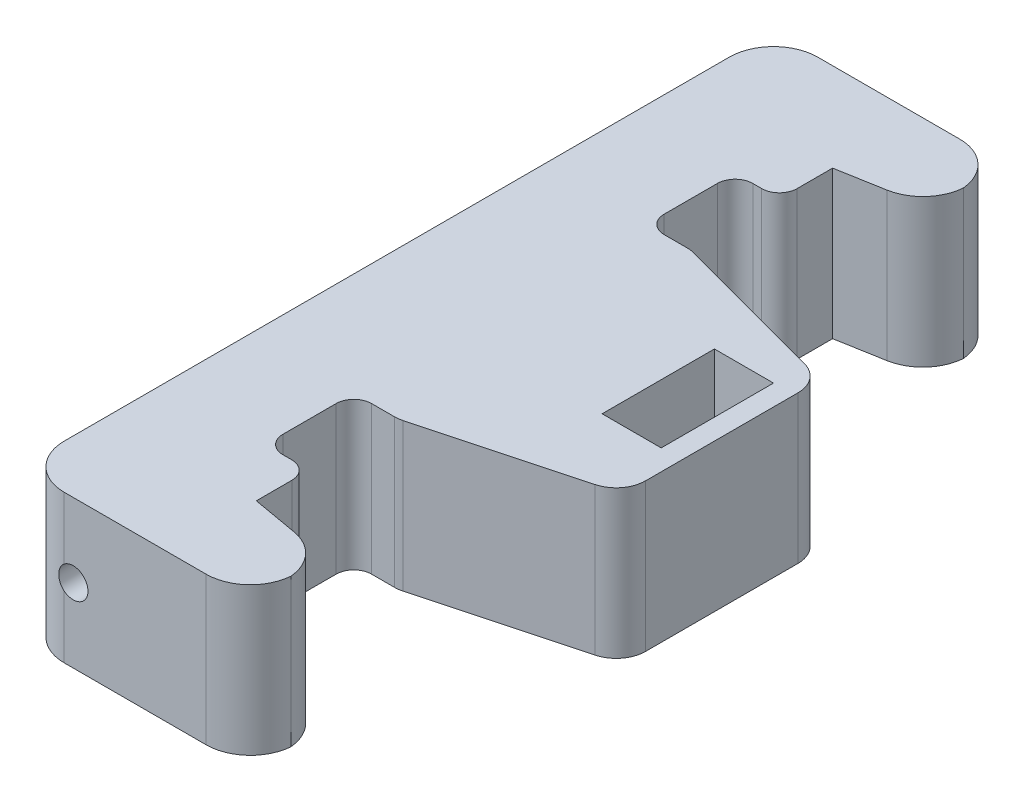
SolidWorks part; units mm, degrees
ref_plane "Front Plane" through (0, 0, 0) normal (0, 0, 1) x (1, 0, 0)
ref_plane "Top Plane" through (0, 0, 0) normal (0, 1, 0) x (1, 0, 0)
ref_plane "Right Plane" through (0, 0, 0) normal (1, 0, 0) x (0, 0, -1)
sketch "Sketch1" plane through (0, 0, 0) normal (0, 1, 0) x (1, 0, 0)
  line L0 (-13.97, 32.385) -> (13.97, -32.385) construction
  line L1 (-13.97, 32.385) -> (13.97, 32.385)
  line L2 (-13.97, 32.385) -> (-13.97, -32.385)
  line L3 (-13.97, -32.385) -> (13.97, -32.385)
  line L4 (13.97, 32.385) -> (13.97, -32.385)
  line L5 (-13.97, -32.385) -> (13.97, 32.385) construction
  line L7 (13.97, 32.385) -> (5.842, 32.385)
  line L8 (13.97, 32.385) -> (13.97, 12.573)
  line L9 (13.97, 12.573) -> (5.842, 12.573)
  line L10 (5.842, 32.385) -> (5.842, 12.573)
  line L11 (13.97, -32.385) -> (5.842, -32.385)
  line L12 (13.97, -32.385) -> (13.97, -12.573)
  line L13 (13.97, -12.573) -> (5.842, -12.573)
  line L14 (5.842, -32.385) -> (5.842, -12.573)
  line L15 (5.842, 12.573) -> (-1.27, 12.573)
  line L16 (5.842, 12.573) -> (5.842, 24.765)
  line L17 (5.842, 24.765) -> (-1.27, 24.765)
  line L18 (-1.27, 12.573) -> (-1.27, 24.765)
  line L23 (5.842, -12.573) -> (-1.27, -12.573)
  line L24 (5.842, -12.573) -> (5.842, -24.765)
  line L25 (5.842, -24.765) -> (-1.27, -24.765)
  line L26 (-1.27, -12.573) -> (-1.27, -24.765)
  line L28 (-1.27, 12.573) -> (-5.08, 12.573)
  line L29 (-1.27, 12.573) -> (-1.27, 20.193)
  line L30 (-1.27, 20.193) -> (-5.08, 20.193)
  line L31 (-5.08, 12.573) -> (-5.08, 20.193)
  line L32 (-1.27, -12.573) -> (-5.08, -12.573)
  line L33 (-1.27, -12.573) -> (-1.27, -20.193)
  line L34 (-1.27, -20.193) -> (-5.08, -20.193)
  line L35 (-5.08, -12.573) -> (-5.08, -20.193)
  point P4 (0, 0)
  dimension "D1" = 27.94
  dimension "D2" = 64.77
  dimension "D3" = 19.812
  dimension "D4" = 8.128
  dimension "D5" = 19.812
  dimension "D6" = 8.128
  dimension "D7" = 12.7
  dimension "D8" = 7.62
  dimension "D9" = 7.62
  dimension "D10" = 12.7
  dimension "D11" = 7.62
  dimension "D12" = 3.81
  dimension "D13" = 7.62
  dimension "D14" = 3.81
extrude "Boss-Extrude1" add sketch "Sketch1" along normal blind 12.7 contours L35 L32 L23 L15 L28 L31 L30 L18 L17 L10 L1 L2 L3 L14 L25 L26 L34 region at (-2.7087, 0, 0)
sketch "Sketch2" plane through (0, 12.7, 0) normal (0, 1, 0) x (1, 0, 0)
  line L0 (-1.27, 24.765) -> (5.842, 26.019)
  line L1 (5.842, 32.385) -> (5.842, 24.765) construction
  line L2 (5.842, 24.765) -> (-1.27, 24.765) construction
  line L3 (-1.27, -24.765) -> (5.842, -26.019)
  line L4 (5.842, -32.385) -> (5.842, -24.765) construction
  line L5 (5.842, -24.765) -> (-1.27, -24.765) construction
  line L11 (-1.27, 24.765) -> (5.842, 24.765)
  line L12 (5.842, 24.765) -> (5.842, 26.019)
  line L17 (-1.27, -24.765) -> (5.842, -24.765)
  line L18 (5.842, -24.765) -> (5.842, -26.019)
  line L19 (-1.27, 12.573) -> (13.97, 8.4895)
  line L20 (13.97, 12.573) -> (-5.08, 12.573) construction
  line L21 (13.97, 12.573) -> (13.97, -12.573) construction
  line L22 (-1.27, -12.573) -> (13.97, -8.4895)
  line L23 (13.97, -12.573) -> (-5.08, -12.573) construction
  line L24 (13.97, 8.4895) -> (13.97, 12.573)
  line L25 (13.97, 12.573) -> (-1.27, 12.573)
  line L26 (13.97, -8.4895) -> (13.97, -12.573)
  line L27 (13.97, -12.573) -> (-1.27, -12.573)
  point P24 (-1.27, -12.573)
  point P34 (-1.27, 12.573)
  dimension "D1" = 10
  dimension "D2" = 10
  dimension "D3" = 15
  dimension "D4" = 15
extrude "Cut-Extrude1" cut sketch "Sketch2" against normal through all
fillet "Fillet4" radius 1.524 6 edges at (-1.27, 6.35, 20.193) (-5.08, 6.35, 20.193) (-5.08, 6.35, 12.573) (-5.08, 6.35, -12.573) (-5.08, 6.35, -20.193) (-1.27, 6.35, -20.193)
fillet "Fillet5" radius 3.81 6 edges at (-13.97, 6.35, 32.385) (-13.97, 6.35, -32.385) (5.842, 6.35, -32.385) (5.842, 6.35, -26.019) (5.842, 6.35, 32.385) (5.842, 6.35, 26.019)
sketch "Sketch3" plane through (0, 0, 32.385) normal (0, 0, 1) x (1, 0, 0)
  line L0 (-10.16, 0) -> (2.032, 0) construction
  circle A0 centre (-9.392, 6.35) radius 1.27
  dimension "D1" = 2.54
  dimension "D2" = 6.35
extrude "Cut-Extrude2" cut sketch "Sketch3" against normal through all
sketch "Sketch4" plane through (0, 12.7, 0) normal (0, 1, 0) x (1, 0, 0)
  line L0 (0, 0) -> (13.97, 0) construction
  line L1 (7.112, 6.223) -> (12.192, 6.223)
  line L2 (7.112, 6.223) -> (7.112, -3.429)
  line L3 (7.112, -3.429) -> (12.192, -3.429)
  line L4 (12.192, 6.223) -> (12.192, -3.429)
  line L7 (13.97, 8.4895) -> (13.97, -8.4895) construction
  line L8 (-13.97, 28.575) -> (-13.97, -28.575) construction
  dimension "D1" = 9.652
  dimension "D2" = 6.223
  dimension "D3" = 21.082
  dimension "D4" = 5.08
extrude "Cut-Extrude3" cut sketch "Sketch4" against normal through all
fillet "Fillet6" radius 2.54 4 edges at (-1.27, 6.35, 12.573) (-1.27, 6.35, -12.573) (13.97, 6.35, 8.4895) (13.97, 6.35, -8.4895)
